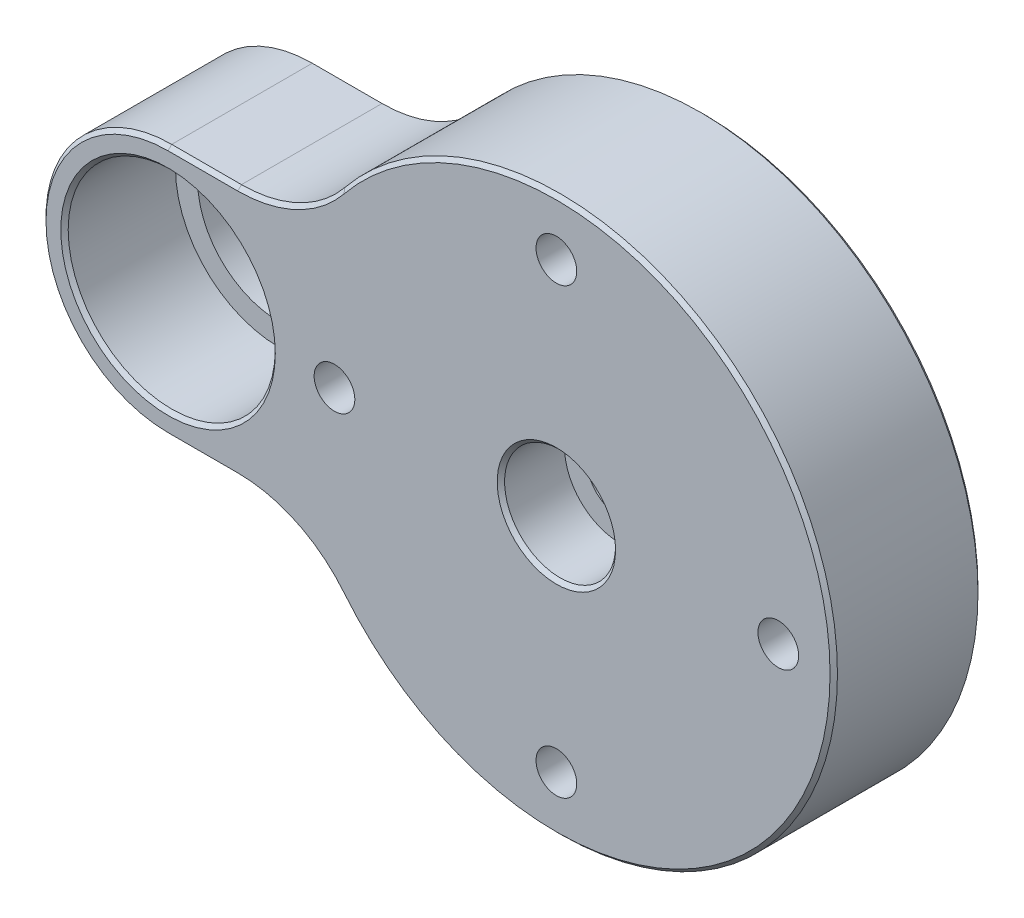
SolidWorks part; units mm, degrees
material "Alumina"
ref_plane "Plan de face" through (0, 0, 0) normal (0, 0, 1) x (1, 0, 0)
ref_plane "Plan de dessus" through (0, 0, 0) normal (0, 1, 0) x (1, 0, 0)
ref_plane "Plan de droite" through (0, 0, 0) normal (1, 0, 0) x (0, 0, -1)
sketch "Sketch1" plane through (0, 0, 0) normal (0, 0, 1) x (1, 0, 0)
  line L1 (-22.5, -22.5) -> (22.5, -22.5)
  line L2 (-22.5, -22.5) -> (-22.5, 22.5)
  line L3 (-22.5, 22.5) -> (22.5, 22.5)
  line L4 (22.5, -22.5) -> (22.5, 22.5)
  line L5 (-22.5, -22.5) -> (22.5, 22.5) construction
  line L6 (-22.5, 22.5) -> (22.5, -22.5) construction
  line L10 (0, 0) -> (-52.5, 0) construction
  line L14 (-52.5, 17) -> (-43.0726, 17)
  line L15 (-52.5, -17) -> (-43.0726, -17)
  arc A1 (-52.5, 17) -> (-52.5, -17) centre (-52.5, 0) ccw
  arc A2 (-29.1031, -23.6486) -> (-29.1031, 23.6486) centre (0, 0) ccw
  arc A3 (-29.1031, -23.6486) -> (-43.0726, -17) centre (-43.0726, -35) ccw
  arc A4 (-29.1031, 23.6486) -> (-43.0726, 17) centre (-43.0726, 35) cw
  point P0 (0, 0)
  dimension "D6" = 34
  dimension "D7" = 75
  dimension "D3" = 18
  dimension "D1" = 45
  dimension "D2" = 45
  dimension "D4" = 52.5
extrude "Boss-Extrude1" add sketch "Sketch1" along normal blind 20 contours L1 L4 L3 L2 | A4 L4 L1 L2 L3 region at (0, 0, 0) region at (-47.7863, 15.6933, 0)
extrude "Cut-Extrude2" cut sketch "Sketch1<3>" along normal blind 5 contours L1 L4 L3 L2 | L4 L3 L2 L1 region at (0, 0, 0)
sketch "Sketch1<3>" plane through (0, 0, 0) normal (0, 0, 1) x (1, 0, 0) same geometry as "Sketch1"
hole_wizard "CBORE for M8 Hex Socket Head Cap Screw1" positions "Sketch2" profile "Sketch3" counterbore size "M8" standard "ISO"
sketch "Sketch2" plane through (0, 0, 20) normal (0, 0, 1) x (1, 0, 0)
  point P0 (0, 0)
sketch "Sketch3" plane through (0, 0, 20) normal (1, 0, 0) x (0, -1, 0)
  line L0 (0, 0) -> (0, 25.7039)
  line L1 (0, 25.7039) -> (4.5, 23)
  line L2 (4.5, 23) -> (4.5, 8.6)
  line L3 (4.5, 8.6) -> (7.5, 8.6)
  line L4 (7.5, 8.6) -> (7.5, 0)
  line L5 (7.5, 0) -> (0, 0)
  line L10 (0, 25.7039) -> (-4.5, 23) construction
  line L11 (0, -6.35) -> (0, 107.95) construction
  dimension "Hole Dia." = 9
  dimension "Hole Depth" = 23
  dimension "C'Bore Dia." = 15
  dimension "C'Bore Depth" = 8.6
  dimension "Drill Angle" = 118
fillet "Fillet2" radius 2.5 4 edges at (22.5, 22.5, 2.5) (22.5, -22.5, 2.5) (-22.5, -22.5, 2.5) (-22.5, 22.5, 2.5)
sketch "Sketch4" plane through (0, 0, 0) normal (0, 0, -1) x (-1, 0, 0)
  circle A0 centre (52.5, 0) radius 11
  dimension "D1" = 22
  dimension "D2" = 52.5
extrude "Cut-Extrude3" cut sketch "Sketch4" against normal blind 6
sketch "Sketch5" plane through (0, 0, 6) normal (0, 0, -1) x (-1, 0, 0)
  circle A0 centre (52.5, 0) radius 14
  circle A1 centre (52.5, 0) radius 11 construction
  dimension "D1" = 28
extrude "Cut-Extrude4" cut sketch "Sketch5" against normal through all and the other way blind 1
chamfer "Chamfer1" distance 0.5 angle 45 23 edges at (-66.5, 0, 20) (7.5, 0, 20) (-35.3371, 18.7469, 20) (-63.5, 0, 0) (22.5, 0, 0) (21.7678, -21.7678, 0) (21.7678, 21.7678, 0) (0, -22.5, 0) (0, 22.5, 0) (-21.7678, -21.7678, 0) (-21.7678, 21.7678, 0) (-22.5, 0, 0) (-35.3371, 18.7469, 0) (-47.7863, 17, 0) (-69.5, 0, 0) (37.5, 0, 0) (-47.7863, -17, 0) (-35.3371, -18.7469, 0) (-47.7863, 17, 20) (-69.5, 0, 20) (37.5, 0, 20) (-47.7863, -17, 20) (-35.3371, -18.7469, 20)
hole_wizard "CBORE for M5 Hex Socket Head Cap Screw1" positions "Sketch6" profile "Sketch7" counterbore size "M5" standard "ISO" end condition through all
sketch "Sketch6" plane through (0, 0, 0) normal (0, 0, -1) x (-1, 0, 0)
  circle A0 centre (0, 0) radius 30 construction
  point P0 (0, 30)
  point P2 (-30, 0)
  point P4 (0, -30)
  point P6 (30, 0)
  dimension "D1" = 60
sketch "Sketch7" plane through (0, 30, 0) normal (1, 0, 0) x (0, 1, 0)
  line L0 (0, 0) -> (0, 20)
  line L1 (0, 20) -> (2.75, 20)
  line L3 (2.75, 20) -> (2.75, 5.4)
  line L4 (2.75, 5.4) -> (5, 5.4)
  line L5 (5, 5.4) -> (5, 0)
  line L7 (5, 0) -> (0, 0)
  line L11 (0, -6.35) -> (0, 107.95) construction
  dimension "Thru Hole Dia." = 5.5
  dimension "Thru Hole Depth" = 20
  dimension "C'Bore Dia." = 10
  dimension "C'Bore Depth" = 5.4
